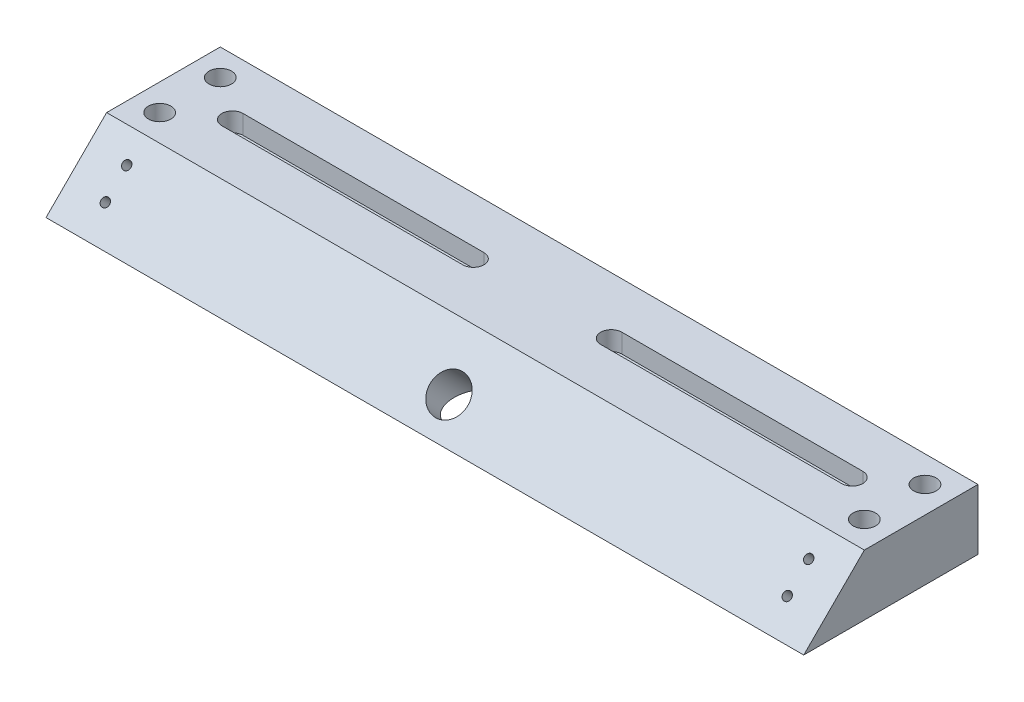
SolidWorks part; units mm, degrees
material "6061-T6 (SS)"
ref_plane "Front Plane" through (0, 0, 0) normal (0, 0, 1) x (1, 0, 0)
ref_plane "Top Plane" through (0, 0, 0) normal (0, 1, 0) x (1, 0, 0)
ref_plane "Right Plane" through (0, 0, 0) normal (1, 0, 0) x (0, 0, -1)
sketch "Sketch1" plane through (0, 0, 0) normal (0, 1, 0) x (1, 0, 0)
  line L1 (-127, -31.75) -> (127, -31.75)
  line L2 (-127, -31.75) -> (-127, 31.75)
  line L3 (-127, 31.75) -> (127, 31.75)
  line L4 (127, -31.75) -> (127, 31.75)
  line L5 (0, 31.75) -> (0, -31.75) construction
  line L6 (-127, 0) -> (127, 0) construction
  point P0 (0, 0)
  dimension "D1" = 254
  dimension "D2" = 63.5
extrude "Boss-Extrude1" add sketch "Sketch1" along normal blind 20.32
chamfer "Chamfer1" distance 25.4 angle 45 1 edges at (0, 20.32, 31.75)
sketch "Sketch2" plane through (0, 20.32, 0) normal (0, 1, 0) x (1, 0, 0)
  line L0 (0, -6.35) -> (0, 31.75) construction
  line L1 (-127, -6.35) -> (127, -6.35) construction
  line L2 (127, 31.75) -> (-127, 31.75) construction
  line L3 (0, 12.7) -> (-127, 12.7) construction
  line L4 (-127, 31.75) -> (-127, -6.35) construction
  line L6 (-107.442, 9.144) -> (-19.558, 9.144)
  line L7 (-107.442, 9.144) -> (-107.442, 16.256)
  line L8 (-107.442, 16.256) -> (-19.558, 16.256)
  line L9 (-19.558, 9.144) -> (-19.558, 16.256)
  line L10 (-63.5, 16.256) -> (-63.5, 9.144) construction
  line L11 (-107.442, 12.7) -> (-19.558, 12.7) construction
  arc A0 (-103.886, 16.256) -> (-103.886, 9.144) centre (-103.886, 12.7) ccw
  arc A1 (-23.114, 16.256) -> (-23.114, 9.144) centre (-23.114, 12.7) cw
  point P10 (-63.5, 12.7)
  dimension "D1" = 80.772
  dimension "D2" = 7.112
extrude "Cut-Extrude1" cut sketch "Sketch2" against normal blind 6.35 contours A1 L8 A0 L6 region at (-63.5, 20.32, -12.7)
sketch "Sketch3" plane through (0, 20.32, 0) normal (0, 1, 0) x (1, 0, 0)
  line L0 (0, 0) -> (0, 31.75) construction
  line L1 (127, 31.75) -> (-127, 31.75) construction
  line L2 (0, 12.7) -> (-127, 12.7) construction
  line L4 (-127, 31.75) -> (-127, -6.35) construction
  line L5 (-127, -6.35) -> (127, -6.35) construction
  circle A0 centre (-118.11, 2.54) radius 3.7719
  circle A1 centre (-118.11, 22.86) radius 3.7719
  circle A2 centre (118.11, 2.54) radius 3.7719
  circle A3 centre (118.11, 22.86) radius 3.7719
  dimension "D3" = 7.5438
  dimension "D1" = 8.89
  dimension "D2" = 8.89
extrude "Cut-Extrude2" cut sketch "Sketch3" against normal through all
sketch "Sketch4" plane through (0, 13.335, 13.335) normal (0, 0.7071, 0.7071) x (1, 0, 0)
  line L0 (-127, -4.4901) -> (0, -4.4901) construction
  line L1 (-127, -18.8585) -> (-127, 9.8783) construction
  line L2 (0, -4.4901) -> (0, -18.8585) construction
  line L3 (-127, -18.8585) -> (127, -18.8585) construction
  line L4 (-114.3, -18.8585) -> (-114.3, 9.8783) construction
  line L7 (127, -18.8585) -> (-127, -18.8585) construction
  line L8 (-127, 9.8783) -> (127, 9.8783) construction
  line L9 (-114.3, 9.8783) -> (-139.9347, 9.8783) construction
  line L10 (-139.9347, 9.8783) -> (-139.9364, 9.7624) construction
  circle A1 centre (-114.3, -8.6985) radius 1.4224
  circle A11 centre (-114.3, 1.4615) radius 1.4224
  circle A12 centre (114.3, -8.6985) radius 1.4224
  circle A13 centre (114.3, 1.4615) radius 1.4224
  dimension "D1" = 12.7
  dimension "D3" = 2.8448
  dimension "D4" = 2.8448
  dimension "D2" = 10.16
  dimension "D5" = 20.32
ref_plane "Midplane" through (0, 0, 0) normal (-1, 0, 0) x (0, 0, 1)
mirror "Mirror1" about plane through (0, 0, 0) normal (-1, 0, 0) of "Cut-Extrude1"
extrude "Cut-Extrude3" cut sketch "Sketch4" against normal blind 7.366
sketch "Sketch5" plane through (0, 13.335, 13.335) normal (0, 0.7071, 0.7071) x (1, 0, 0)
  line L0 (0, 9.8783) -> (0, -18.8585) construction
  line L1 (-127, 9.8783) -> (127, 9.8783) construction
  line L2 (127, -18.8585) -> (-127, -18.8585) construction
  circle A0 centre (0, -7.4285) radius 6.35
  dimension "D1" = 12.7
  dimension "D2" = 11.43
extrude "Cut-Extrude4" cut sketch "Sketch5" against normal through all
